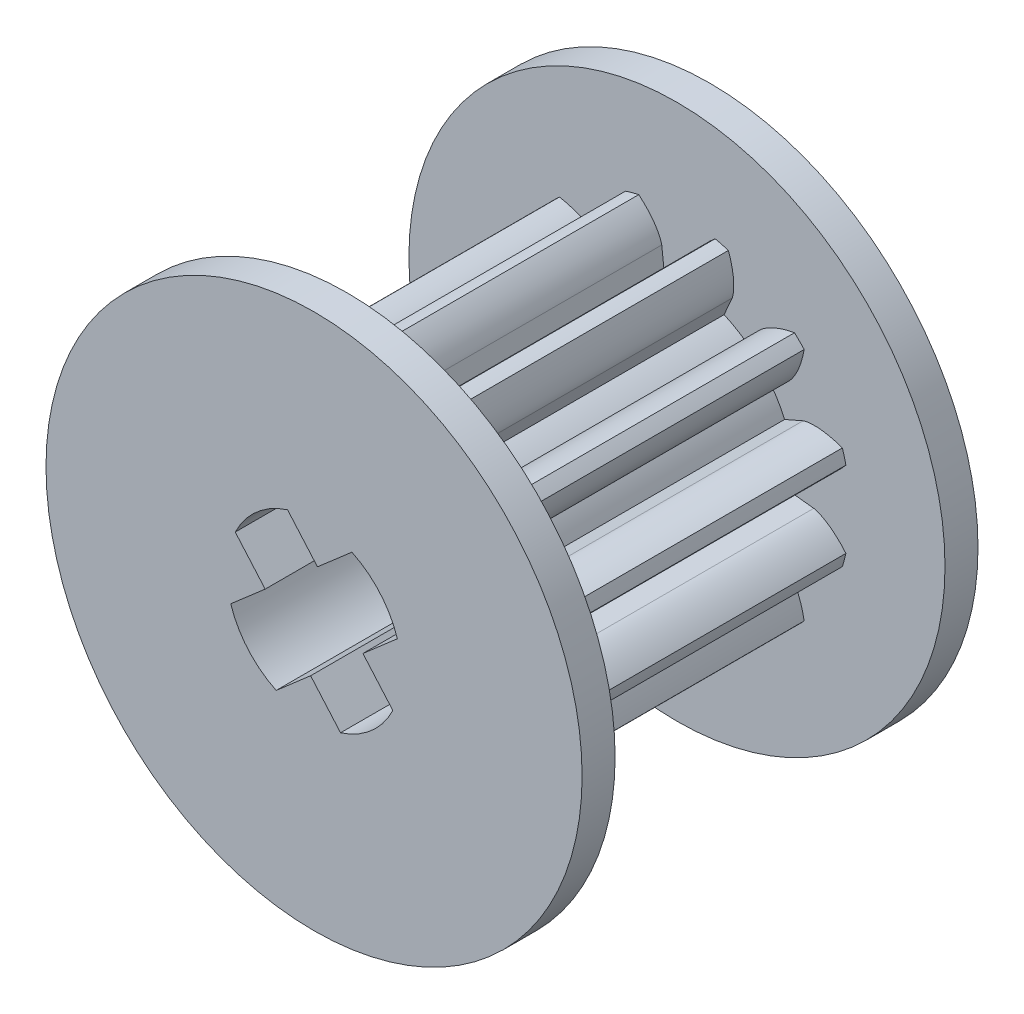
SolidWorks part; units mm, degrees
ref_plane "Front Plane" through (0, 0, 0) normal (0, 0, 1) x (1, 0, 0)
ref_plane "Top Plane" through (0, 0, 0) normal (0, 1, 0) x (1, 0, 0)
ref_plane "Right Plane" through (0, 0, 0) normal (1, 0, 0) x (0, 0, -1)
ref_axis "Axis1" [suppressed] through (0, 0, 71.2135) along (0, 0, -1)
sketch "Sketch1" plane through (0, 0, 0) normal (0, 0, 1) x (1, 0, 0)
  circle A0 centre (0, 0) radius 3.5625
  circle A1 centre (0, 0) radius 4.1723
  circle A2 centre (0, 0) radius 3.75
  circle A3 centre (0, 0) radius 4.5
  circle A4 centre (0, 0) radius 5.25
  dimension "Pitch" = 9
  dimension "Addendum" = 10.5
  dimension "Clearance" = 7.5
  dimension "Base" = 8.3447
  dimension "Root" = 7.125
extrude "Boss-Extrude1" add sketch "Sketch1" along normal blind 10 contours A4
sketch "Sketch3" plane through (0, 0, 0) normal (0, 0, 1) x (1, 0, 0)
  line L0 (0.4615, 4.1467) -> (0, 0) construction
  line L1 (0.7855, 4.0977) -> (0, 0) construction
  line L2 (1.1046, 4.0235) -> (0, 0) construction
  line L3 (1.4168, 3.9244) -> (0, 0) construction
  line L4 (1.7204, 3.8011) -> (0, 0) construction
  line L5 (2.0133, 3.6544) -> (0, 0) construction
  line L6 (2.2938, 3.4852) -> (0, 0) construction
  line L7 (2.5602, 3.2945) -> (0, 0) construction
  line L8 (2.8108, 3.0835) -> (0, 0) construction
  line L9 (3.044, 2.8534) -> (0, 0) construction
  line L10 (3.2585, 2.6058) -> (0, 0) construction
  line L11 (0.7855, 4.0977) -> (0.4636, 4.1594) construction
  line L12 (3.2585, 2.6058) -> (1.2119, 5.1651) construction
  line L13 (1.1046, 4.0235) -> (0.4725, 4.197) construction
  line L14 (1.4168, 3.9244) -> (0.4922, 4.2582) construction
  line L15 (1.7204, 3.8011) -> (0.5262, 4.3416) construction
  line L16 (2.0133, 3.6544) -> (0.5782, 4.4451) construction
  line L17 (2.2938, 3.4852) -> (0.6514, 4.5662) construction
  line L18 (2.5602, 3.2945) -> (0.7489, 4.702) construction
  line L19 (2.8108, 3.0835) -> (0.8734, 4.8495) construction
  line L20 (3.044, 2.8534) -> (1.0271, 5.0051) construction
  line L21 (0, 0) -> (0, 4.5) construction
  line L22 (0, 0) -> (0.5874, 4.4615)
  line L23 (0, 0) -> (-0.5874, 4.4615)
  line L24 (0.4615, 4.1467) -> (0.3941, 3.5406)
  line L25 (-0.4615, 4.1467) -> (-0.3941, 3.5406)
  circle A0 centre (0, 0) radius 4.1723 construction
  circle A1 centre (0, 0) radius 4.5 construction
  arc A2 (3.2585, 2.6058) -> (0.4615, 4.1467) centre (0, 0) ccw construction
  circle A3 centre (0, 0) radius 3.5625 construction
  circle A4 centre (0, 0) radius 3.5625
  circle A5 centre (0, 0) radius 5.25 construction
  circle A6 centre (0, 0) radius 5.25
  spline S0 degree 3 poles (0.4615, 4.1467) (0.464, 4.1637) (0.473, 4.2013) (0.4941, 4.2666) (0.5286, 4.35) (0.6061, 4.5031) (0.722, 4.6743) (0.9298, 4.9199) (1.0915, 5.0686) (1.2119, 5.1651) knots 0 0 0 0 0.040008 0.090018 0.16003 0.250047 0.489907 0.639935 1 1 1 1
  spline S1 degree 3 poles (-0.4615, 4.1467) (-0.464, 4.1637) (-0.473, 4.2013) (-0.4941, 4.2666) (-0.5286, 4.35) (-0.6061, 4.5031) (-0.722, 4.6743) (-0.9298, 4.9199) (-1.0915, 5.0686) (-1.2119, 5.1651) knots 0 0 0 0 0.040008 0.090018 0.16003 0.250047 0.489907 0.639935 1 1 1 1
  point P18 (0, 0)
  dimension "D2" = 45
  dimension "D3" = 0.3277
  dimension "D4" = 3.2769
  dimension "D5" = 0.6554
  dimension "D6" = 0.9831
  dimension "D7" = 1.3108
  dimension "D8" = 1.6385
  dimension "D9" = 1.9662
  dimension "D10" = 2.2939
  dimension "D11" = 2.6216
  dimension "D12" = 2.9492
  dimension "D13" = 15
  dimension "D1" = 11
extrude "Cut-Extrude3" cut sketch "Sketch3" along normal through all contours S1 L25 A4 L24 S0 A6 region at (0, 4.5519, 0)
fillet "Fillet2" [suppressed] radius 0.05
pattern_circular "CirPattern1" count 12 over 360 about axis through (0, 0, 71.2135) along (0, 0, -1) of "Cut-Extrude3", "Fillet2"
ref_plane "Plane2" through (0, 0, 5) normal (0, 0, 1) x (1, 0, 0)
sketch "Sketch6" plane through (0, 0, 10) normal (0, 0, 1) x (1, 0, 0)
  circle A0 centre (0, 0) radius 8.125
  dimension "D1" = 16.25
extrude "Boss-Extrude2" add sketch "Sketch6" along normal blind 1
mirror "Mirror1" about plane through (0, 0, 5) normal (0, 0, 1) of "Boss-Extrude2"
sketch "Sketch5" plane through (0, 0, 0) normal (0, 0, 1) x (1, 0, 0)
  line L0 (-0.8803, 2.2327) -> (0.0791, 1.1286) construction
  line L1 (-1.1286, 0.0791) -> (-2.088, 1.1833) construction
  line L2 (-2.2327, -0.8803) -> (-1.1286, 0.0791) construction
  line L3 (-0.0791, -1.1286) -> (-1.1833, -2.088) construction
  line L4 (0.8803, -2.2327) -> (-0.0791, -1.1286) construction
  line L5 (1.1286, -0.0791) -> (2.088, -1.1833) construction
  line L6 (2.2327, 0.8803) -> (1.1286, -0.0791) construction
  line L7 (0.0791, 1.1286) -> (1.1833, 2.088) construction
  line L8 (-0.8803, 2.2327) -> (0.0791, 1.1286)
  line L9 (-1.1286, 0.0791) -> (-2.088, 1.1833)
  line L10 (-2.2327, -0.8803) -> (-1.1286, 0.0791)
  line L11 (-0.0791, -1.1286) -> (-1.1833, -2.088)
  line L12 (0.8803, -2.2327) -> (-0.0791, -1.1286)
  line L13 (1.1286, -0.0791) -> (2.088, -1.1833)
  line L14 (2.2327, 0.8803) -> (1.1286, -0.0791)
  line L15 (0.0791, 1.1286) -> (1.1833, 2.088)
  line L16 (0.1039, 1.4813) -> (1.1479, 2.3885)
  line L17 (-0.8033, 2.5253) -> (0.1039, 1.4813)
  line L18 (-1.4813, 0.1039) -> (-2.3885, 1.1479)
  line L19 (-2.5253, -0.8033) -> (-1.4813, 0.1039)
  line L20 (-0.1039, -1.4813) -> (-1.1479, -2.3885)
  line L21 (0.8033, -2.5253) -> (-0.1039, -1.4813)
  line L22 (1.4813, -0.1039) -> (2.3885, -1.1479)
  line L23 (2.5253, 0.8033) -> (1.4813, -0.1039)
  arc A0 (-0.8803, 2.2327) -> (-2.088, 1.1833) centre (0, 0) ccw construction
  arc A1 (-2.2327, -0.8803) -> (-1.1833, -2.088) centre (0, 0) ccw construction
  arc A2 (0.8803, -2.2327) -> (2.088, -1.1833) centre (0, 0) ccw construction
  arc A3 (2.2327, 0.8803) -> (1.1833, 2.088) centre (0, 0) ccw construction
  arc A4 (-0.8803, 2.2327) -> (-2.088, 1.1833) centre (0, 0) ccw
  arc A5 (-2.2327, -0.8803) -> (-1.1833, -2.088) centre (0, 0) ccw
  arc A6 (0.8803, -2.2327) -> (2.088, -1.1833) centre (0, 0) ccw
  arc A7 (2.2327, 0.8803) -> (1.1833, 2.088) centre (0, 0) ccw
  arc A10 (2.5253, 0.8033) -> (1.1479, 2.3885) centre (0, 0) ccw
  arc A11 (-0.8033, 2.5253) -> (-2.3885, 1.1479) centre (0, 0) ccw
  arc A13 (-2.5253, -0.8033) -> (-1.1479, -2.3885) centre (0, 0) ccw
  arc A14 (0.8033, -2.5253) -> (2.3885, -1.1479) centre (0, 0) ccw
  dimension "D1" = 0.25
extrude "Cut-Extrude4" cut sketch "Sketch5" along normal through all both and the other way through all contours L14 A7 L15 L8 A4 L9 L10 A5 L11 L12 A6 L13 | L21 A14 L22 L23 A10 L16 L17 A11 L18 L19 A13 L20 A7 L14 L13 A6 L12 L11 A5 L10 L9 A4 L8 L15 region at (0, 0, 0) region at (0.6727, 1.881, 0)
equation "\"Module\"= .75"
equation "\"numTeeth\"= 12"
equation "\"pressureAngle\"= 22deg"
equation "\"toothRadius\"= .05"
equation "\"Pitch@Sketch1\"=\"Module\"*\"numTeeth\""
equation "\"Addendum@Sketch1\"=\"Pitch@Sketch1\"+\"Module\"*2"
equation "\"Clearance@Sketch1\"=\"Pitch@Sketch1\"-\"Module\"*2"
equation "\"Base@Sketch1\"=\"Pitch@Sketch1\"*cos(\"pressureAngle\")"
equation "\"Root@Sketch1\"=\"Pitch@Sketch1\"-\"Module\"*1.25*2"
equation "\"D4@Sketch3\"= \"Base@Sketch1\" * pi / 8"
equation "\"D3@Sketch3\"= \"D4@Sketch3\" / 10"
equation "\"D5@Sketch3\"=\"D3@Sketch3\"*2"
equation "\"D6@Sketch3\"=\"D3@Sketch3\"*3"
equation "\"D7@Sketch3\"=\"D3@Sketch3\"*4"
equation "\"D8@Sketch3\"=\"D3@Sketch3\"*5"
equation "\"D9@Sketch3\"=\"D3@Sketch3\"*6"
equation "\"D10@Sketch3\"=\"D3@Sketch3\"*7"
equation "\"D11@Sketch3\"=\"D3@Sketch3\"*8"
equation "\"D12@Sketch3\"=\"D3@Sketch3\"*9"
equation "\"D13@Sketch3\"=180/\"numTeeth\""
equation "\"D1@CirPattern1\"=\"numTeeth\""
equation "\"D1@Fillet2\"= \"toothRadius\""
